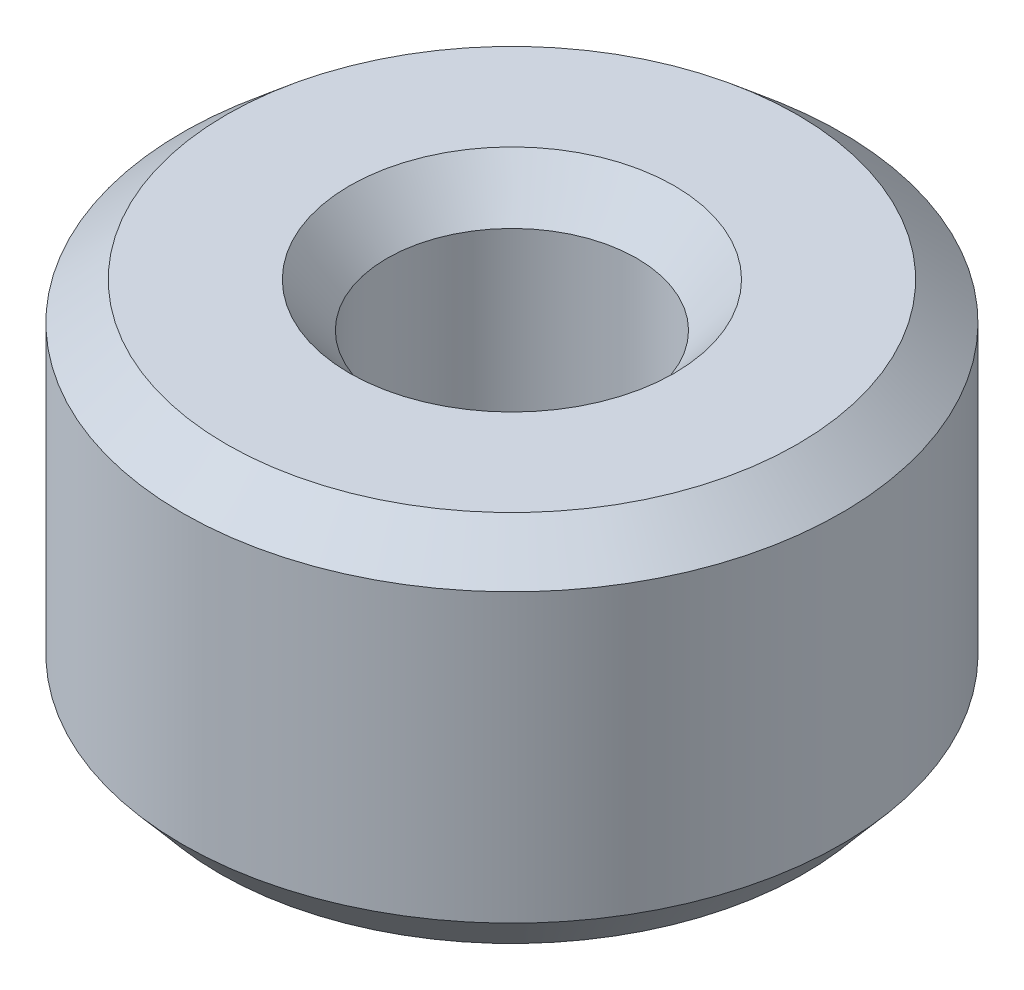
SolidWorks part; units mm, degrees
ref_plane "Front Plane" through (0, 0, 0) normal (0, 0, 1) x (1, 0, 0)
ref_plane "Top Plane" through (0, 0, 0) normal (0, 1, 0) x (1, 0, 0)
ref_plane "Right Plane" through (0, 0, 0) normal (1, 0, 0) x (0, 0, -1)
sketch "Sketch1" plane through (0, 0, 0) normal (0, 1, 0) x (1, 0, 0)
  circle A0 centre (0, 0) radius 10
  dimension "SLEEVE_OD" = 20
extrude "Boss-Extrude1" add sketch "Sketch1" along normal blind 11.1828
sketch "Sketch2" plane through (0, 0, 0) normal (0, 1, 0) x (1, 0, 0)
  circle A0 centre (0, 0) radius 3.79
  dimension "BORE_D" = 7.5799
extrude "Cut-Extrude1" cut sketch "Sketch2" along normal through all
chamfer "Chamfer1" distance 1.1369 angle 49.644 4 edges at (0, 11.1828, 3.79) (0, 0, 3.79) (0, 0, 10) (0, 11.1828, 10) first distance on face at (0, 11.1828, 3.79) first distance on face at (0, 0, 3.79) first distance on face at (0, 11.1828, 10)
